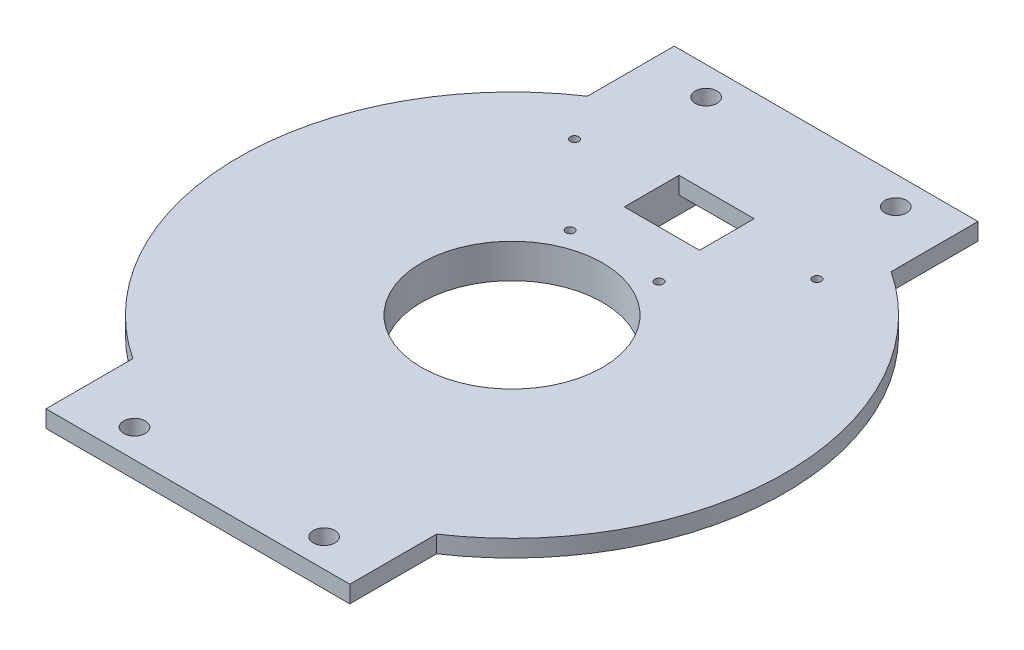
SolidWorks part; units mm, degrees
ref_plane "Front Plane" through (0, 0, 0) normal (0, 0, 1) x (1, 0, 0)
ref_plane "Top Plane" through (0, 0, 0) normal (0, 1, 0) x (1, 0, 0)
ref_plane "Right Plane" through (0, 0, 0) normal (1, 0, 0) x (0, 0, -1)
sketch "Sketch1" plane through (0, 0, 0) normal (0, 1, 0) x (1, 0, 0)
  circle A0 centre (0, 0) radius 26.5
  circle A1 centre (0, 0) radius 69
  dimension "D1" = 53
  dimension "D2" = 138
extrude "Boss-Extrude1" add sketch "Sketch1" along normal blind 10
sketch "Sketch2" plane through (0, 0, 0) normal (0, -1, 0) x (1, 0, 0)
  line L0 (0, 0) -> (-13, -30) construction
  line L1 (-8.7574, -30) -> (-13, -34.2426)
  line L2 (-8.7574, -30) -> (-13, -25.7574)
  line L3 (-13, -25.7574) -> (-17.2426, -30)
  line L4 (-13, -34.2426) -> (-17.2426, -30)
  line L5 (-8.7574, -30) -> (-17.2426, -30) construction
  line L6 (-13, -25.7574) -> (-13, -34.2426) construction
  line L7 (17.2426, -30) -> (13, -34.2426)
  line L8 (17.2426, -30) -> (13, -25.7574)
  line L9 (13, -25.7574) -> (8.7574, -30)
  line L10 (13, -34.2426) -> (8.7574, -30)
  line L11 (17.2426, -30) -> (8.7574, -30) construction
  line L12 (13, -25.7574) -> (13, -34.2426) construction
  line L13 (0, 0) -> (13, -30) construction
  line L14 (-35.46, -53.7582) -> (-13, -30) construction
  line L15 (-31.2174, -53.7582) -> (-35.46, -58.0009)
  line L16 (-31.2174, -53.7582) -> (-35.46, -49.5156)
  line L17 (-35.46, -49.5156) -> (-39.7026, -53.7582)
  line L18 (-35.46, -58.0009) -> (-39.7026, -53.7582)
  line L19 (-31.2174, -53.7582) -> (-39.7026, -53.7582) construction
  line L20 (-35.46, -49.5156) -> (-35.46, -58.0009) construction
  line L21 (39.7026, -53.7582) -> (35.46, -58.0009)
  line L22 (39.7026, -53.7582) -> (35.46, -49.5156)
  line L23 (35.46, -49.5156) -> (31.2174, -53.7582)
  line L24 (35.46, -58.0009) -> (31.2174, -53.7582)
  line L25 (39.7026, -53.7582) -> (31.2174, -53.7582) construction
  line L26 (35.46, -49.5156) -> (35.46, -58.0009) construction
  line L27 (13, -30) -> (35.46, -53.7582) construction
  point P0 (13, -30)
  point P4 (-13, -30)
  point P11 (35.46, -53.7582)
  point P13 (-35.46, -53.7582)
  dimension "D1" = 26
  dimension "D2" = 30
  dimension "D3" = 6
  dimension "D4" = 64.4
  dimension "D5" = 64.4
  dimension "D6" = 70.92
  dimension "D7" = 6
extrude "Cut-Extrude1" cut sketch "Sketch2" against normal blind 4.5 contours L4 L1 L2 L3 | L18 L15 L16 L17 | L10 L7 L8 L9 | L24 L21 L22 L23 region at (-13, 0, -30) region at (13, 0, -30) region at (-35.46, 0, -53.7582) region at (35.46, 0, -53.7582)
sketch "Sketch3" plane through (0, 0, 0) normal (0, -1, 0) x (1, 0, 0)
  line L1 (11, -59.875) -> (-11, -59.875)
  line L2 (11, -59.875) -> (11, -43.875)
  line L3 (11, -43.875) -> (-11, -43.875)
  line L4 (-11, -59.875) -> (-11, -43.875)
  line L5 (11, -59.875) -> (-11, -43.875) construction
  line L6 (11, -43.875) -> (-11, -59.875) construction
  point P0 (0, -51.875)
  dimension "D1" = 51.875
  dimension "D2" = 16
  dimension "D3" = 22
extrude "Cut-Extrude2" cut sketch "Sketch3" against normal through all
sketch "Sketch4" plane through (0, 0, 0) normal (0, -1, 0) x (1, 0, 0)
  line L0 (31.2174, -53.7582) -> (35.46, -58.0009) construction
  line L1 (35.46, -58.0009) -> (39.7026, -53.7582) construction
  line L2 (39.7026, -53.7582) -> (35.46, -49.5156) construction
  line L3 (35.46, -49.5156) -> (31.2174, -53.7582) construction
  line L4 (8.7574, -30) -> (13, -34.2426) construction
  line L5 (13, -34.2426) -> (17.2426, -30) construction
  line L6 (17.2426, -30) -> (13, -25.7574) construction
  line L7 (13, -25.7574) -> (8.7574, -30) construction
  line L8 (-39.7026, -53.7582) -> (-35.46, -58.0009) construction
  line L9 (-35.46, -58.0009) -> (-31.2174, -53.7582) construction
  line L10 (-31.2174, -53.7582) -> (-35.46, -49.5156) construction
  line L11 (-35.46, -49.5156) -> (-39.7026, -53.7582) construction
  line L12 (-17.2426, -30) -> (-13, -34.2426) construction
  line L13 (-13, -34.2426) -> (-8.7574, -30) construction
  line L14 (-8.7574, -30) -> (-13, -25.7574) construction
  line L15 (-13, -25.7574) -> (-17.2426, -30) construction
  line L16 (31.2174, -53.7582) -> (35.46, -58.0009) construction
  line L17 (35.46, -58.0009) -> (39.7026, -53.7582) construction
  line L18 (39.7026, -53.7582) -> (35.46, -49.5156) construction
  line L19 (35.46, -49.5156) -> (31.2174, -53.7582) construction
  line L20 (8.7574, -30) -> (13, -34.2426) construction
  line L21 (13, -34.2426) -> (17.2426, -30) construction
  line L22 (17.2426, -30) -> (13, -25.7574) construction
  line L23 (13, -25.7574) -> (8.7574, -30) construction
  line L24 (-39.7026, -53.7582) -> (-35.46, -58.0009) construction
  line L25 (-35.46, -58.0009) -> (-31.2174, -53.7582) construction
  line L26 (-31.2174, -53.7582) -> (-35.46, -49.5156) construction
  line L27 (-35.46, -49.5156) -> (-39.7026, -53.7582) construction
  line L28 (-17.2426, -30) -> (-13, -34.2426) construction
  line L29 (-13, -34.2426) -> (-8.7574, -30) construction
  line L30 (-8.7574, -30) -> (-13, -25.7574) construction
  line L31 (-13, -25.7574) -> (-17.2426, -30) construction
  circle A0 centre (-13, -30) radius 1.25
  circle A1 centre (13, -30) radius 1.25
  circle A2 centre (-35.46, -53.7582) radius 1.25
  circle A3 centre (35.46, -53.7582) radius 1.25
  dimension "D1" = 2.5
extrude "Cut-Extrude3" cut sketch "Sketch4" against normal through all
sketch "Sketch5" plane through (0, 0, 0) normal (0, -1, 0) x (1, 0, 0)
  line L0 (-43, -46.7253) -> (-11, -43.875) construction
  line L1 (11, -43.875) -> (43, -46.7253) construction
  line L2 (-44.9013, 44.9013) -> (-11, -43.875) construction
  line L3 (11, -43.875) -> (44.9013, 44.9013) construction
  circle A2 centre (-44.9013, 44.9013) radius 1.9
  circle A3 centre (44.9013, 44.9013) radius 1.9
  circle A4 centre (-43, -46.7253) radius 1.9
  circle A5 centre (43, -46.7253) radius 1.9
  dimension "D1" = 89.8026
  dimension "D4" = 3.8
  dimension "D5" = 63.5
  dimension "D7" = 86
  dimension "D2" = 63.5
  dimension "D3" = 63.5
  dimension "D6" = 63.5
extrude "Boss-Extrude2" add sketch "Sketch5" along normal blind 3.5 contours A3 | A2 | A4 | A5 region at (44.9013, 0, 44.9013)
sketch "Sketch6" plane through (0, 10, 0) normal (0, 1, 0) x (1, 0, 0)
  line L0 (-7.425, 0) -> (7.425, 0) construction
  line L1 (-44.45, 66.5146) -> (44.45, 66.5146) construction
  line L2 (-44.45, 66.5146) -> (-44.45, 91.9146)
  line L3 (-44.45, 91.9146) -> (44.45, 91.9146)
  line L4 (44.45, 66.5146) -> (44.45, 91.9146)
  line L5 (-44.45, -66.5146) -> (44.45, -66.5146) construction
  line L6 (44.45, -66.5146) -> (44.45, -91.9146)
  line L7 (-44.45, -66.5146) -> (-44.45, -91.9146)
  line L8 (-44.45, -91.9146) -> (44.45, -91.9146)
  line L9 (-26.8356, 91.9146) -> (-26.8356, 83.6397) construction
  line L10 (-26.8356, 83.6397) -> (-26.8356, 75.3648) construction
  circle A0 centre (0, 0) radius 80
  circle A1 centre (-26.8356, 83.6397) radius 3.175
  circle A2 centre (28.6621, 83.6397) radius 3.175
  circle A3 centre (28.6621, -83.6397) radius 3.175
  circle A4 centre (-26.8356, -83.6397) radius 3.175
  point P8 (0, 66.5146)
  circle M14 centre (0, 0) radius 69
  dimension "D1" = 88.9
  dimension "D2" = 160
  dimension "D4" = 6.35
  dimension "D3" = 25.4
extrude "Boss-Extrude3" add sketch "Sketch6" against normal blind 5 contours A0 M14 | A0 L4 L3 L2 | A0 L7 L8 L6 region at (-0.0419, 10, -83.2926) region at (0, 10, -77.7373) region at (-0.0419, 10, 83.2926)
chamfer "Chamfer1" distance 1 angle 20 4 edges at (43, -3.5, -48.6253) (44.9013, -3.5, 43.0013) (-43, -3.5, -48.6253) (-44.9013, -3.5, 43.0013) first distance on face at (43, -3.5, -48.6253) first distance on face at (44.9013, -3.5, 43.0013) first distance on face at (-43, -3.5, -48.6253) first distance on face at (-44.9013, -3.5, 43.0013)
sketch "Sketch7" plane through (0, 0, 0) normal (0, -1, 0) x (1, 0, 0)
  line L1 (-11, -59.875) -> (11, -59.875)
  line L2 (-11, -59.875) -> (-11, -69)
  line L3 (-11, -69) -> (11, -69)
  line L4 (11, -59.875) -> (11, -69)
  circle A0 centre (0, 0) radius 69 construction
extrude "Cut-Extrude4" cut sketch "Sketch7" against normal up to surface (5 mm away) up to face at (0, 5, 69)
sketch "Sketch8" plane through (0, 0, 0) normal (0, -1, 0) x (1, 0, 0)
  line L0 (0, 0) -> (-66.0526, 19.9514)
  line L1 (0, 0) -> (-65.1681, -22.6743)
  line L2 (0, 0) -> (0, 18.7046) construction
  line L3 (0, 0) -> (65.1681, -22.6743)
  line L4 (0, 0) -> (66.0526, 19.9514)
  circle A0 centre (0, 0) radius 61.6
  arc A1 (11, -68.1175) -> (-11, -68.1175) centre (0, 0) ccw construction
  arc A2 (11, -68.1175) -> (-11, -68.1175) centre (0, 0) ccw
  circle A3 centre (-44.9013, 44.9013) radius 1.9 construction
  circle A4 centre (44.9013, 44.9013) radius 1.536 construction
  circle A5 centre (-44.9013, 44.9013) radius 1.536
  circle A6 centre (-44.9013, 44.9013) radius 1.536
  circle A7 centre (43, -46.7253) radius 1.536 construction
  circle A8 centre (-43, -46.7253) radius 1.536 construction
  circle A9 centre (44.9013, 44.9013) radius 1.536
  circle A10 centre (43, -46.7253) radius 1.536
  circle A11 centre (-43, -46.7253) radius 1.536
  arc M19 (11, -68.1175) -> (-11, -68.1175) centre (0, 0) ccw
  dimension "D1" = 0
  dimension "D2" = 30
  dimension "D3" = 30
extrude "Cut-Extrude5" cut sketch "Sketch8" against normal blind 2 contours A0 L0 L1 M19 | A0 L3 L4 M19 region at (-64.2865, 0, -1.334) region at (64.2865, 0, -1.334)
fillet "Fillet1" radius 5 1 edges at (0, 5, 69)
fillet "Fillet2" radius 2 6 edges at (61.8707, 2, -21.527) (61.5867, 2, -1.2779) (62.7104, 2, 18.9419) (-61.8707, 2, -21.527) (-61.5867, 2, -1.2779) (-62.7104, 2, 18.9419)
